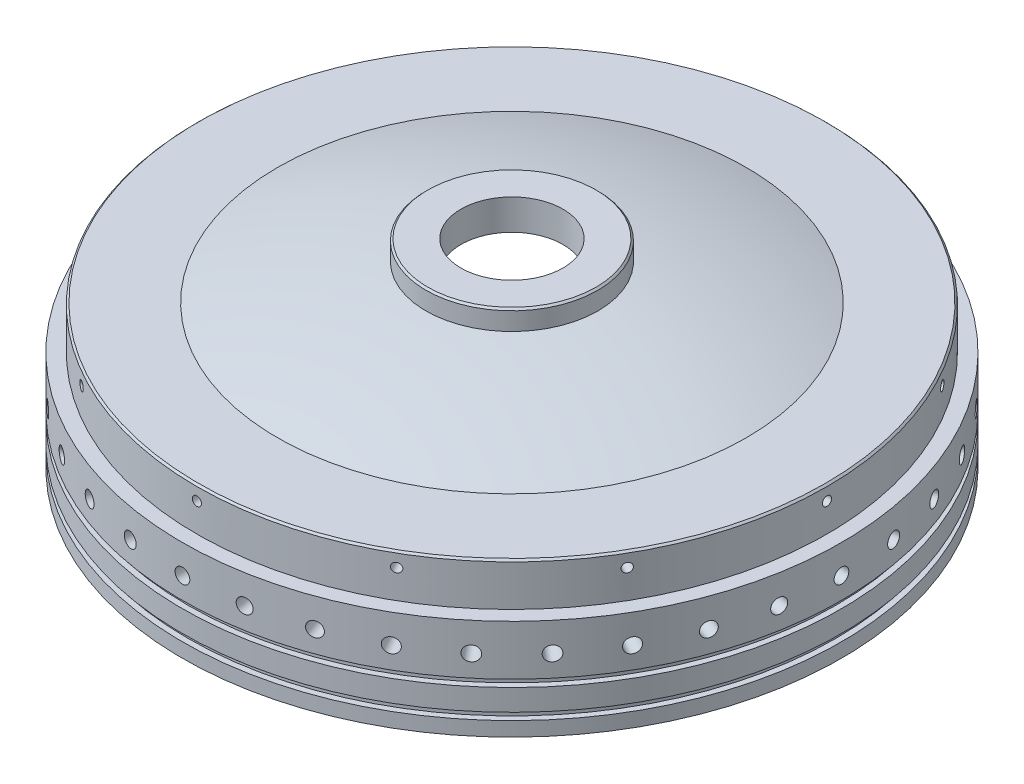
SolidWorks part; units mm, degrees
material "6061-T6 (SS)"
ref_plane "Front Plane" through (0, 0, 0) normal (0, 0, 1) x (1, 0, 0)
ref_plane "Top Plane" through (0, 0, 0) normal (0, 1, 0) x (1, 0, 0)
ref_plane "Right Plane" through (0, 0, 0) normal (1, 0, 0) x (0, 0, -1)
sketch "Sketch1" plane through (0, 0, 0) normal (0, 0, 1) x (1, 0, 0)
  line L0 (0, 81.7273) -> (0, 75.3773)
  line L1 (136.525, 0) -> (146.05, 0)
  line L2 (146.05, 0) -> (146.05, 6.35)
  line L4 (139.6229, 44.45) -> (146.05, 44.45)
  line L5 (130.81, 22.225) -> (130.81, 44.45)
  line L6 (146.05, 6.35) -> (143.51, 6.35)
  line L7 (103.8227, 63.5) -> (139.6229, 63.5)
  line L8 (143.51, 6.35) -> (143.51, 9.525)
  line L9 (143.51, 9.525) -> (146.05, 9.525)
  line L10 (146.05, 19.05) -> (143.51, 19.05)
  line L11 (143.51, 19.05) -> (143.51, 22.225)
  line L12 (143.51, 22.225) -> (146.05, 22.225)
  line L13 (146.05, 9.525) -> (146.05, 19.05)
  line L14 (146.05, 22.225) -> (146.05, 44.45)
  line L15 (139.6229, 63.5) -> (139.6229, 44.45)
  line L17 (136.525, 0) -> (136.525, 22.225)
  line L18 (136.525, 22.225) -> (130.81, 22.225)
  arc A0 (103.8227, 63.5) -> (0, 81.7273) centre (0, -223.0727) ccw
  arc A1 (130.81, 44.45) -> (0, 75.3773) centre (0, -216.7227) ccw
  dimension "D5" = 146.05
  dimension "D1" = 304.8
  dimension "D7" = 3.175
  dimension "D9" = 292.1
  dimension "D10" = 2.54
  dimension "D2" = 6.4271
  dimension "D3" = 9.525
  dimension "D6" = 44.45
  dimension "D8" = 6.35
  dimension "D11" = 6.35
  dimension "D12" = 19.05
  dimension "D13" = 19.05
  dimension "D15" = 15.24
revolve "Revolve1" add sketch "Sketch1" angle 360 about L0
ref_plane "Plane1" through (0, 81.7273, 0) normal (0, 1, 0) x (1, 0, 0)
sketch "Sketch2" plane through (0, 81.7273, 0) normal (0, 1, 0) x (1, 0, 0)
  circle A0 centre (0, 0) radius 38.1
  dimension "D1" = 76.2
extrude "Boss-Extrude1" add sketch "Sketch2" along normal blind 6.35 and the other way up to next
ref_plane "Plane2" through (-146.05, 0, 0) normal (-1, 0, 0) x (0, 0, 1)
hole_wizard "5/16-18 Tapped Hole1" positions "Sketch3" profile "Sketch5" tap size "5/16-18" standard "ANSI Inch"
sketch "Sketch3" plane through (-146.05, 0, 0) normal (-1, 0, 0) x (0, 0, 1)
  line L0 (0, 31.75) -> (0, 0) construction
  line L2 (146.05, 44.45) -> (-146.05, 44.45) construction
  point P0 (0, 31.75)
  dimension "D1" = 12.7
cosmetic thread "Hole Thread1" parameters "D1"=10.16, "D2"=7.9375
sketch "Sketch5" plane through (-146.05, 31.75, 0) normal (0, 1, 0) x (0, 0, 1)
  line L0 (0, 0) -> (0, 14.6611)
  line L1 (0, 14.6611) -> (3.2639, 12.7)
  line L2 (3.2639, 12.7) -> (3.2639, 0)
  line L5 (3.2639, 0) -> (0, 0)
  line L10 (0, 14.6611) -> (-3.2639, 12.7) construction
  line L11 (0, -6.35) -> (0, 107.95) construction
  dimension "Tap Drill Dia." = 6.5278
  dimension "Tap Drill Depth" = 12.7
  dimension "Drill Angle" = 118
pattern_circular "CirPattern1" count 36 over 360 about axis through (0, 44.45, 0) along (0, 1, 0) of "5/16-18 Tapped Hole1"
ref_plane "Plane3" through (-139.6229, 0, 0) normal (-1, 0, 0) x (0, 0, 1)
hole_wizard "#10-32 Tapped Hole1" positions "Sketch6" profile "Sketch7" tap size "#10-32" standard "ANSI Inch"
sketch "Sketch6" plane through (-139.6229, 0, 0) normal (-1, 0, 0) x (0, 0, 1)
  line L0 (0, 0) -> (0, 57.15) construction
  line L3 (146.05, 44.45) -> (-146.05, 44.45) construction
  point P0 (0, 57.15)
  dimension "D1" = 12.7
sketch "Sketch7" plane through (-139.6229, 57.15, 0) normal (0, 1, 0) x (0, 0, 1)
  line L0 (0, 0) -> (0, 13.1513)
  line L1 (0, 13.1513) -> (2.0193, 11.938)
  line L2 (2.0193, 11.938) -> (2.0193, 0)
  line L5 (2.0193, 0) -> (0, 0)
  line L10 (0, 13.1513) -> (-2.0193, 11.938) construction
  line L11 (0, -6.35) -> (0, 107.95) construction
  dimension "Tap Drill Dia." = 4.0386
  dimension "Tap Drill Depth" = 11.938
  dimension "Drill Angle" = 118
cosmetic thread "Hole Thread4" parameters "D1"=9.652, "D2"=4.826
hole_wizard "2-4.5 Tapped Hole1" positions "Sketch8" profile "Sketch9" tap size "2-4.5" standard "ANSI Inch"
sketch "Sketch8" plane through (0, 88.0773, 0) normal (0, 1, 0) x (1, 0, 0)
  point P0 (0, 0)
sketch "Sketch9" plane through (0, 88.0773, 0) normal (1, 0, 0) x (0, 0, 1)
  line L0 (0, 0) -> (0, 132.2102)
  line L1 (0, 132.2102) -> (22.6212, 118.618)
  line L2 (22.6212, 118.618) -> (22.6212, 0)
  line L5 (22.6212, 0) -> (0, 0)
  line L10 (0, 132.2102) -> (-22.6212, 118.618) construction
  line L11 (0, -6.35) -> (0, 107.95) construction
  dimension "Tap Drill Dia." = 45.2425
  dimension "Tap Drill Depth" = 118.618
  dimension "Drill Angle" = 118
cosmetic thread "Hole Thread3" parameters "D1"=19.9273, "D2"=50.8
chamfer "Chamfer2" distance 0.7937 angle 45 2 edges at (-38.1, 88.0773, 0) (-139.6229, 63.5, 0)
pattern_circular "CirPattern2" count 12 over 360 about axis through (0, 63.5, 0) along (0, 1, 0) of "#10-32 Tapped Hole1"
